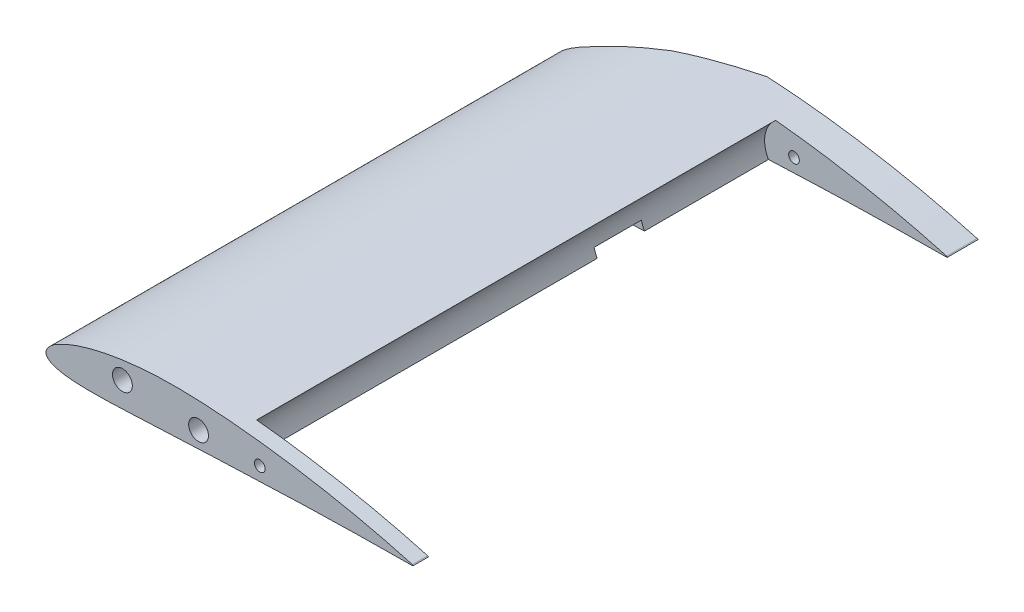
SolidWorks part; units mm, degrees
material "Balsa"
ref_plane "Front Plane" through (0, 0, 0) normal (0, 0, 1) x (1, 0, 0)
ref_plane "Top Plane" through (0, 0, 0) normal (0, 1, 0) x (1, 0, 0)
ref_plane "Right Plane" through (0, 0, 0) normal (1, 0, 0) x (0, 0, -1)
curve "曲線2"
  spline degree 3 poles (200, 0.26, 0) (196.6701, 1.1665, 0) (190.0264, 2.975, 0) (176.7171, 6.2635, 0) (160.0733, 9.8968, 0) (140.0541, 13.4784, 0) (120.0503, 16.4141, 0) (100.0354, 18.5082, 0) (80.0223, 19.8143, 0) (63.3151, 19.8275, 0) (49.9753, 18.9046, 0) (39.957, 17.689, 0) (29.917, 15.8963, 0) (21.5972, 13.7404, 0) (14.9301, 11.563, 0) (9.903, 9.5074, 0) (5.6136, 7.2843, 0) (1.8903, 4.6252, 0) (-1.3508, 0.3484, 0) (2.1476, -2.9224, 0) (5.7173, -4.2063, 0) (9.9686, -5.0729, 0) (14.9893, -5.5135, 0) (21.6639, -5.8253, 0) (30.0021, -5.8019, 0) (40.0043, -5.522, 0) (49.9995, -4.9891, 0) (63.3329, -4.3655, 0) (79.9968, -3.5653, 0) (100.0006, -2.8138, 0) (119.9979, -1.9794, 0) (139.9972, -1.2688, 0) (159.998, -0.746, 0) (176.6662, -0.4806, 0) (189.9997, -0.3058, 0) (196.6666, -0.2753, 0) (200, -0.26, 0) knots 0 0 0 0 0.025305 0.050488 0.10052 0.150191 0.199587 0.24874 0.297716 0.346601 0.371103 0.395726 0.42057 0.445825 0.458702 0.47192 0.485786 0.493461 0.506863 0.516148 0.522766 0.535269 0.547551 0.559786 0.584229 0.608681 0.633151 0.657622 0.706558 0.755482 0.804406 0.85332 0.902221 0.951113 0.975557 1 1 1 1
sketch "草圖4" plane through (0, 0, 0) normal (0, 0, 1) x (1, 0, 0)
  line L8 (26.3929, -5.7959) -> (118.9885, -5.7959) construction
  spline S1 degree 2 poles (120, 0.156) (120.5501, 0) (120, -0.156) knots 0 0 0 1 1 1
  spline S2 degree 3 poles (120, 0.156) (118.0021, 0.6999) (114.0158, 1.785) (106.0302, 3.7581) (96.044, 5.9381) (84.0324, 8.087) (72.0302, 9.8485) (60.0213, 11.1049) (48.0134, 11.8886) (37.9891, 11.8965) (29.9852, 11.3428) (23.9742, 10.6134) (17.9502, 9.5378) (12.9583, 8.2442) (8.9581, 6.9378) (5.9418, 5.7044) (3.3681, 4.3706) (1.1342, 2.7751) (-0.8105, 0.209) (1.2885, -1.7534) (3.4304, -2.5238) (5.9811, -3.0437) (8.9936, -3.3081) (12.9983, -3.4952) (18.0013, -3.4812) (24.0026, -3.3132) (29.9997, -2.9935) (37.9998, -2.6193) (47.9981, -2.1392) (60.0003, -1.6883) (71.9988, -1.1877) (83.9983, -0.7613) (95.9988, -0.4476) (105.9997, -0.2883) (113.9998, -0.1835) (118, -0.1652) (120, -0.156) knots 0 0 0 0 0.025305 0.050488 0.10052 0.150191 0.199587 0.24874 0.297716 0.346601 0.371103 0.395726 0.42057 0.445825 0.458702 0.47192 0.485786 0.493461 0.506863 0.516148 0.522766 0.535269 0.547551 0.559786 0.584229 0.608681 0.633151 0.657622 0.706558 0.755482 0.804406 0.85332 0.902221 0.951113 0.975557 1 1 1 1
  point P0 (0, 0)
extrude "填料-伸長1" add sketch "草圖4" along normal blind 185
sketch "草圖2" plane through (0, 0, 0) normal (0, 0, -1) x (-1, 0, 0)
  line L0 (-49.9391, 3.2561) -> (-25, 5) construction
  line L1 (-31.2982, 15.2311) -> (-54.8503, 15.2311) construction
  circle A0 centre (-25, 5) radius 3.25
  circle A1 centre (-49.9391, 3.2561) radius 3.25
  dimension "D1" = 6.5
  dimension "D2" = 25
  dimension "D3" = 25
  dimension "D4" = 5
  dimension "D5" = 4
extrude "除料-伸長1" cut sketch "草圖2" against normal through all
sketch "草圖3" plane through (0, 0, 0) normal (0, 1, 0) x (1, 0, 0)
  line L0 (120, 0) -> (-0.0337, 0) construction
  line L1 (70.275, -10) -> (120.275, -10)
  line L2 (70.275, -10) -> (70.275, -180)
  line L3 (70.275, -180) -> (120.275, -180)
  line L4 (120.275, -10) -> (120.275, -180)
  line L6 (-0.0337, -185) -> (120, -185) construction
  line L7 (51.1104, 0) -> (27.6363, -7.6409)
  line L8 (27.6363, -7.6409) -> (9.8855, -15.3784)
  line L9 (9.8855, -15.3784) -> (-0.0337, -18.2322)
  line L10 (-0.0337, 0) -> (-0.0337, -185) construction
  line L11 (-0.0337, -18.2322) -> (-0.0337, 0)
  line L12 (-0.0337, 0) -> (51.1104, 0)
  dimension "D1" = 10
  dimension "D2" = 50
  dimension "D3" = 5
extrude "除料-伸長2" cut sketch "草圖3" against normal through all and the other way through all
sketch "草圖5" plane through (0, 0, 0) normal (0, 0, -1) x (-1, 0, 0)
  circle A0 centre (-70, 3.156) radius 1.75
  dimension "D3" = 3.5
  dimension "D1" = 50
  dimension "D2" = 3
extrude "除料-伸長3" cut sketch "草圖5" against normal through all
sketch "草圖6" plane through (0, 0, 0) normal (0, 0, -1) x (-1, 0, 0)
  circle A0 centre (-70, 3.156) radius 9.6299
extrude "除料-伸長4" cut sketch "草圖6" against normal up to surface (180 mm away) from surface up to face at (87.0958, 1.5668, 180) starting at face at (87.0958, 3.4412, 10)
sketch "草圖7" plane through (0, 0, 0) normal (0, 1, 0) x (1, 0, 0)
  line L0 (61.6349, -10) -> (61.6349, -180) construction
  line L2 (17.6349, -50.6158) -> (17.6349, -25)
  line L3 (17.6349, -25) -> (51.6349, -25)
  line L4 (51.6349, -50.6158) -> (51.6349, -25)
  line L5 (61.6349, -10) -> (120, -10) construction
  line L6 (51.6349, -50.6158) -> (82.522, -50.6158)
  line L7 (8.4126, -66.0861) -> (82.522, -66.0861)
  line L8 (8.4126, -66.0861) -> (8.4126, -50.6158)
  line L9 (8.4126, -50.6158) -> (17.6349, -50.6158)
  line L10 (82.522, -66.0861) -> (82.522, -50.6158)
  dimension "D3" = 10
  dimension "D4" = 15
extrude "除料-伸長5" cut sketch "草圖7" against normal through all and the other way blind 1
